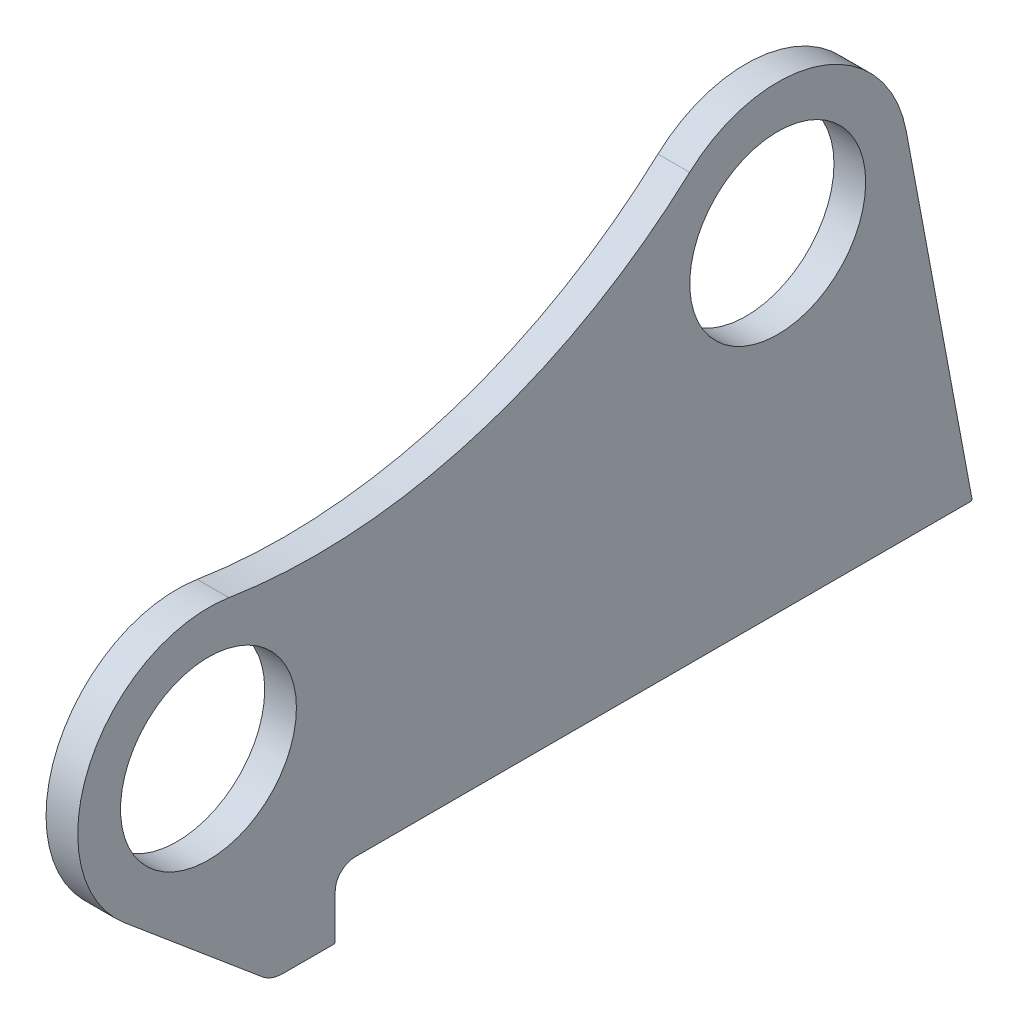
SolidWorks part; units mm, degrees
material "MS-Grade 350"
ref_plane "Front Plane" through (0, 0, 0) normal (0, 0, 1) x (1, 0, 0)
ref_plane "Top Plane" through (0, 0, 0) normal (0, 1, 0) x (1, 0, 0)
ref_plane "Right Plane" through (0, 0, 0) normal (1, 0, 0) x (0, 0, -1)
sketch "Sketch1" plane through (0, 0, 0) normal (1, 0, 0) x (0, 0, -1)
  line L0 (0, -41) -> (0, -12.5)
  line L1 (12.5, 0) -> (402, 0)
  line L3 (402, 0) -> (360.3236, 222.7741)
  line L4 (-133.0582, 36.825) -> (-45.9722, -36.3151)
  line L11 (0, -41) -> (-33.1096, -41)
  line L12 (-80, 100) -> (279.2305, 207.6033) construction
  circle A0 centre (-80, 100) radius 55.5
  circle A1 centre (279.2305, 207.6033) radius 55.5
  arc A2 (-67.0706, 181.4806) -> (-133.0582, 36.825) centre (-80, 100) ccw
  arc A4 (-45.9722, -36.3151) -> (-33.1096, -41) centre (-33.1096, -21) ccw
  arc A5 (0, -12.5) -> (12.5, 0) centre (12.5, -12.5) cw
  arc A9 (360.3236, 222.7741) -> (223.6362, 268.5583) centre (279.2305, 207.6033) ccw
  arc A10 (-67.0706, 181.4806) -> (223.6362, 268.5583) centre (-12.2185, 527.1556) ccw
  point P31 (0, 0)
  dimension "D2" = 100
  dimension "D4" = 82.5
  dimension "D5" = 111
  dimension "D6" = 41
  dimension "D7" = 350
  dimension "D13" = 40.026
  dimension "D20" = 12.5
  dimension "D3" = 20
  dimension "D12" = 402
  dimension "D15" = 16.675
  dimension "D16" = 375
  dimension "D17" = 80
sheet metal parameters "Sheet-Metal1" thickness 20 parameters "D1"=92
base flange "Base-Flange1" sketch "Sketch1" thickness 20 reverse thickness direction no parameters "D1"=92
fillet "Fillet-1.0" radius 1 2 edges at (-10, 0, -402) (-10, -41, 0)
flat pattern "Flat-Pattern1" [suppressed]
sketch "Bend-Lines1" plane through (0, 0, 0) normal (0, 1, 0) x (1, 0, 0)
sketch3d "Bounding-Box1" [suppressed]
  line L0 (-159.6299, -579.154, 0) -> (414.8787, -520.584, 0) construction
  line L1 (-191.1408, -270.0661, 0) -> (383.3678, -211.4961, 0) construction
  line L2 (-159.6299, -579.154, 0) -> (-191.1408, -270.0661, 0) construction
  line L3 (414.8787, -520.584, 0) -> (383.3678, -211.4961, 0) construction
